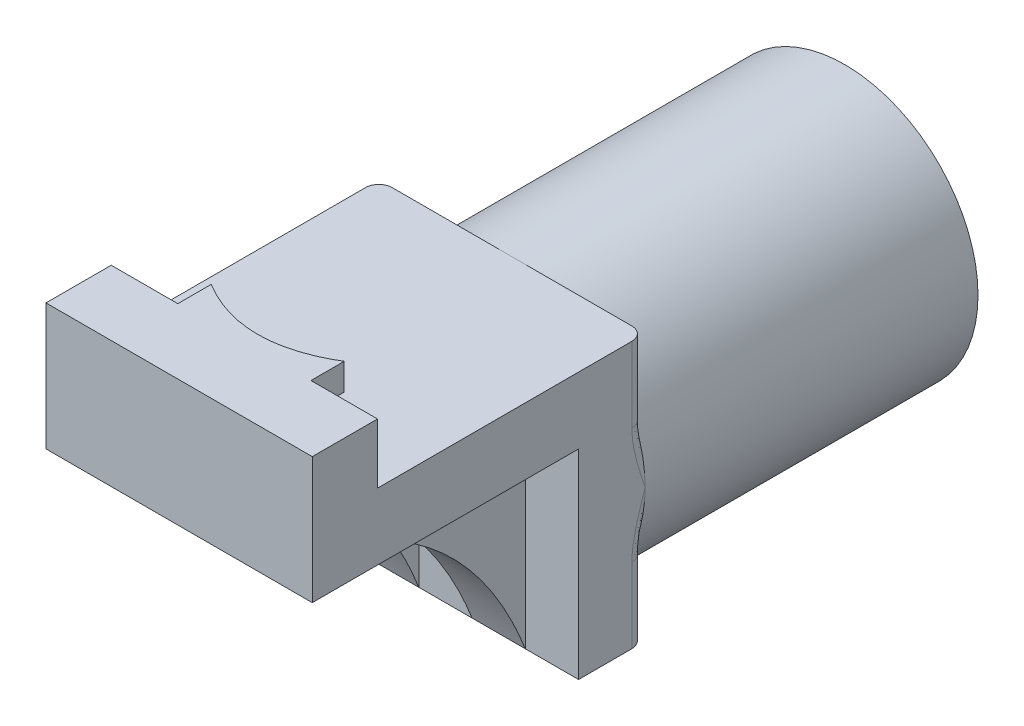
SolidWorks part; units mm, degrees
material "사용자정의 플라스틱"
ref_plane "정면" through (0, 0, 0) normal (0, 0, 1) x (1, 0, 0)
ref_plane "윗면" through (0, 0, 0) normal (0, 1, 0) x (1, 0, 0)
ref_plane "우측면" through (0, 0, 0) normal (1, 0, 0) x (0, 0, -1)
sketch "스케치1" plane through (0, 0, 0) normal (0, 0, 1) x (1, 0, 0)
  circle A0 centre (0, 0) radius 20
  dimension "D1" = 40
extrude "보스-돌출1" add sketch "스케치1" along normal blind 50
sketch "스케치2" plane through (0, 0, 50) normal (0, 0, 1) x (1, 0, 0)
  line L1 (-20, 20) -> (20, 20)
  line L2 (-20, 20) -> (-20, -20)
  line L3 (-20, -20) -> (20, -20)
  line L4 (20, 20) -> (20, -20)
  line L5 (-20, 20) -> (20, -20) construction
  line L6 (-20, -20) -> (20, 20) construction
  point P0 (0, 0)
  dimension "D1" = 40
  dimension "D2" = 40
extrude "보스-돌출2" add sketch "스케치2" along normal blind 50
sketch "스케치3" plane through (0, 20, 0) normal (0, -1, 0) x (0, 0, -1)
  line L1 (-100, 20) -> (-90.2, 20)
  line L2 (-100, 20) -> (-100, -20)
  line L3 (-100, -20) -> (-90.2, -20)
  line L4 (-90.2, 20) -> (-90.2, -20)
  line L5 (-100, -20) -> (-50, -20) construction
  point P5 (-91, -20)
  dimension "D1" = 9.8
extrude "보스-돌출4" add sketch "스케치3" against normal blind 9
sketch "스케치4" plane through (0, 0, 90.2) normal (0, 0, -1) x (-1, 0, 0)
  line L0 (-20, 29) -> (-20, 20) construction
  line L1 (-20, 25) -> (20, 25)
  line L2 (-20, 25) -> (-20, 29)
  line L3 (-20, 29) -> (20, 29)
  line L4 (20, 25) -> (20, 29)
  dimension "D1" = 4
extrude "보스-돌출5" add sketch "스케치4" along normal blind 5
sketch "스케치5" plane through (0, 29, 0) normal (0, 1, 0) x (1, 0, 0)
  line L0 (-20, -85.2) -> (20, -85.2) construction
  line L1 (-20, -85.2) -> (-10, -85.2)
  line L2 (-20, -85.2) -> (-20, -90.2)
  line L3 (-20, -90.2) -> (-10, -90.2)
  line L4 (-10, -85.2) -> (-10, -90.2)
  line L5 (20, -85.2) -> (10, -85.2)
  line L6 (20, -85.2) -> (20, -90.2)
  line L7 (20, -90.2) -> (10, -90.2)
  line L8 (10, -85.2) -> (10, -90.2)
  line L9 (20, -85.2) -> (20, -100) construction
  point P11 (20, -89.2)
  dimension "D1" = 10
  dimension "D2" = 10
  dimension "D3" = 5
  dimension "D4" = 5
extrude "컷-돌출1" cut sketch "스케치5" against normal blind 5
sketch "스케치6" plane through (0, 29, 0) normal (0, 1, 0) x (1, 0, 0)
  line L1 (-10, -85.2) -> (10, -85.2) construction
  line L2 (-10, -90.2) -> (-10, -85.2) construction
  line L3 (10, -85.2) -> (10, -90.2) construction
  spline S0 degree 2 poles (-10, -85.2) (0, -91.2) (10, -85.2) knots 0 0 0 1 1 1
  dimension "D1" = 3
extrude "컷-돌출2" cut sketch "스케치6" against normal blind 5 and the other way through all
sketch "스케치7" plane through (-20, 0, 0) normal (-1, 0, 0) x (0, 0, 1)
  line L0 (90.2, 20) -> (50, 20) construction
  line L1 (100, -20) -> (60, -20)
  line L2 (100, -20) -> (100, 10)
  line L3 (100, 10) -> (60, 10)
  line L4 (60, -20) -> (60, 10)
  line L5 (50, 0) -> (50, -20) construction
  dimension "D1" = 10
  dimension "D2" = 10
extrude "컷-돌출3" cut sketch "스케치7" against normal through all
sketch "스케치8" plane through (0, 10, 0) normal (0, -1, 0) x (1, 0, 0)
  line L0 (20, 60) -> (-20, 60) construction
  line L1 (-12, 60) -> (-4, 60)
  line L2 (-12, 60) -> (-12, 100)
  line L3 (-12, 100) -> (-4, 100)
  line L4 (-4, 60) -> (-4, 100)
  line L5 (20, 100) -> (-20, 100) construction
  line L6 (-20, 100) -> (-20, 60) construction
  line L7 (12, 100) -> (4, 100)
  line L8 (12, 100) -> (12, 60)
  line L9 (12, 60) -> (4, 60)
  line L10 (4, 100) -> (4, 60)
  line L11 (20, 100) -> (20, 60) construction
  dimension "D1" = 8
  dimension "D2" = 8
  dimension "D3" = 8
  dimension "D4" = 8
extrude "보스-돌출6" add sketch "스케치8" along normal blind 30
sketch "스케치9" plane through (-12, 0, 0) normal (-1, 0, 0) x (0, 0, 1)
  line L0 (60, -20) -> (100, -20)
  line L1 (100, -20) -> (100, 10)
  line L3 (60, 10) -> (60, -20) construction
  line L6 (100, 10) -> (60, 10) construction
  spline S0 degree 2 poles (60, -20) (70.5945, 7.0287) (100, 10) knots 0 0 0 1 1 1
  point P11 (71.4333, 10)
  dimension "D1" = 14
  dimension "D2" = 10
extrude "컷-돌출4" cut sketch "스케치9" against normal through all
fillet "필렛1" radius 2 4 edges at (20, -10, 50) (-20, -10, 50) (20, 10, 50) (-20, 10, 50)
sketch "스케치10" plane through (0, 0, 0) normal (0, 0, -1) x (-1, 0, 0)
  circle A0 centre (0, 0) radius 12
  arc A1 (20, 0) -> (18, 8.7178) centre (0, 0) ccw construction
  dimension "D1" = 8
extrude "컷-돌출5" cut sketch "스케치10" against normal blind 50
